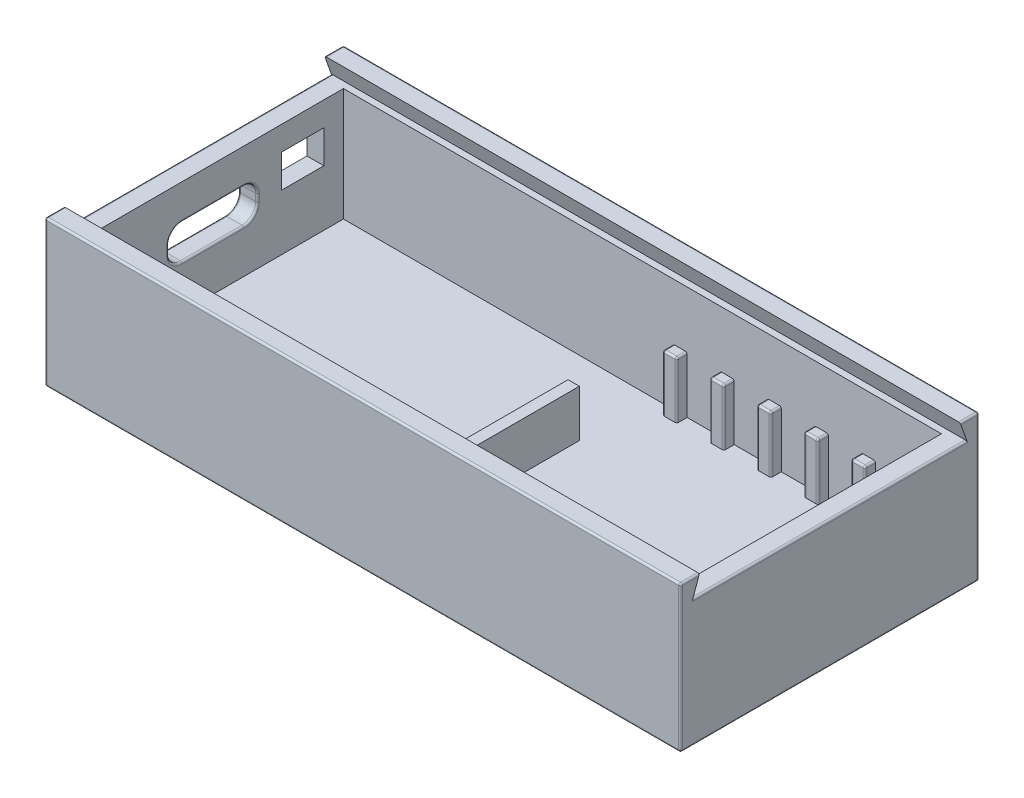
SolidWorks part; units mm, degrees
material "PLA"
ref_plane "前视基准面" through (0, 0, 0) normal (0, 0, 1) x (1, 0, 0)
ref_plane "上视基准面" through (0, 0, 0) normal (0, 1, 0) x (1, 0, 0)
ref_plane "右视基准面" through (0, 0, 0) normal (1, 0, 0) x (0, 0, -1)
sketch "草图1" plane through (0, 0, 0) normal (0, 0, 1) x (1, 0, 0)
  line L0 (0, 0) -> (67.5, 0)
  line L1 (67.5, 0) -> (67.5, 13.5)
  line L2 (67.5, 13.5) -> (65.5, 13.5)
  line L3 (65.5, 13.5) -> (65.5, 1.5)
  line L4 (65.5, 1.5) -> (2, 1.5)
  line L5 (2, 1.5) -> (2, 13.5)
  line L6 (2, 13.5) -> (0, 13.5)
  line L7 (0, 13.5) -> (0, 0)
  dimension "D1" = 63.5
  dimension "D3" = 2
  dimension "D4" = 1.5
  dimension "D6" = 12
extrude "凸台-拉伸1" add sketch "草图1" along normal blind 31.7
sketch "草图3" plane through (0, 1.5, 0) normal (0, 1, 0) x (1, 0, 0)
  line L0 (2, -31.7) -> (65.5, -31.7)
  line L1 (65.5, -31.7) -> (65.5, -29.7)
  line L2 (65.5, -31.7) -> (65.5, 0) construction
  line L3 (65.5, -29.7) -> (2, -29.7)
  line L4 (2, -31.7) -> (2, 0) construction
  line L5 (2, -29.7) -> (2, -31.7)
  dimension "D1" = 2
extrude "凸台-拉伸2" add sketch "草图3" along normal through all
sketch "草图4" plane through (0, 1.5, 0) normal (0, 1, 0) x (1, 0, 0)
  line L0 (2, 0) -> (65.5, 0)
  line L1 (65.5, -29.7) -> (65.5, 0) construction
  line L2 (65.5, -29.7) -> (65.5, 0) construction
  line L3 (65.5, 0) -> (65.5, -2)
  line L4 (65.5, -2) -> (2, -2)
  line L5 (2, -29.7) -> (2, 0) construction
  line L6 (2, -2) -> (2, 0)
  dimension "D1" = 2
extrude "凸台-拉伸3" add sketch "草图4" along normal through all
sketch "草图5" plane through (0, 1.5, 0) normal (0, 1, 0) x (1, 0, 0)
  line L0 (34.3, -6.415) -> (34.3, -25.7073) construction
  line L2 (23.9227, -15.85) -> (46.7103, -15.85) construction
  line L3 (2, -2) -> (65.5, -2) construction
  line L4 (65.5, -29.7) -> (2, -29.7) construction
  line L5 (34.9, -9.85) -> (33.7, -9.85)
  line L6 (33.7, -9.85) -> (33.7, -21.85)
  line L7 (34.9, -9.85) -> (34.9, -21.85)
  line L8 (34.9, -21.85) -> (33.7, -21.85)
  line L9 (2, -29.7) -> (2, -2) construction
  point P14 (34.3, -9.85)
  point P16 (34.9, -15.85)
  point P17 (33.7, -15.85)
  dimension "D1" = 1.2
  dimension "D2" = 32.3
  dimension "D3" = 12
extrude "凸台-拉伸4" add sketch "草图5" along normal blind 5 contours L6 L8 L7 L5
sketch "草图10" plane through (0, 0, 0) normal (-1, 0, 0) x (0, 0, 1)
  line L0 (5.075, 9.1862) -> (7.575, 9.1862) construction
  line L1 (5.075, 8.1862) -> (5.075, 10.1862) construction
  line L2 (7.575, 10.1862) -> (7.575, 8.1862) construction
  line L3 (6.325, 8.1862) -> (6.325, 10.1862) construction
  line L4 (7.575, 8.1862) -> (5.075, 8.1862) construction
  line L5 (5.075, 10.1862) -> (7.575, 10.1862) construction
  line L7 (8.575, 7.4362) -> (4.075, 7.4362)
  line L8 (8.575, 7.4362) -> (8.575, 10.9362)
  line L9 (8.575, 10.9362) -> (4.075, 10.9362)
  line L10 (4.075, 7.4362) -> (4.075, 10.9362)
  line L11 (8.575, 7.4362) -> (4.075, 10.9362) construction
  line L12 (8.575, 10.9362) -> (4.075, 7.4362) construction
  point P12 (6.325, 9.1862)
  dimension "D1" = 3.5
  dimension "D2" = 4.5
extrude "切除-拉伸3" cut sketch "草图10" against normal up to next
chamfer "倒角3" distance 0.2 angle 45 4 edges at (0, 7.4362, 6.325) (0, 9.1862, 8.575) (0, 9.1862, 4.075) (0, 10.9362, 6.325)
sketch "草图11" plane through (0, 0, 0) normal (-1, 0, 0) x (0, 0, 1)
  line L14 (11.13, 8.3362) -> (11.13, 7.5762)
  line L15 (12.58, 6.1262) -> (19.12, 6.1262)
  line L16 (20.57, 7.5762) -> (20.57, 8.3362)
  line L17 (19.12, 9.7862) -> (12.58, 9.7862)
  line L18 (11.13, 8.3362) -> (11.13, 7.5762)
  line L19 (12.58, 6.1262) -> (19.12, 6.1262)
  line L20 (20.57, 7.5762) -> (20.57, 8.3362)
  line L21 (19.12, 9.7862) -> (12.58, 9.7862)
  arc A8 (11.13, 7.5762) -> (12.58, 6.1262) centre (12.58, 7.5762) ccw
  arc A9 (19.12, 6.1262) -> (20.57, 7.5762) centre (19.12, 7.5762) ccw
  arc A10 (20.57, 8.3362) -> (19.12, 9.7862) centre (19.12, 8.3362) ccw
  arc A11 (12.58, 9.7862) -> (11.13, 8.3362) centre (12.58, 8.3362) ccw
  arc A12 (11.13, 7.5762) -> (12.58, 6.1262) centre (12.58, 7.5762) ccw
  arc A13 (19.12, 6.1262) -> (20.57, 7.5762) centre (19.12, 7.5762) ccw
  arc A14 (20.57, 8.3362) -> (19.12, 9.7862) centre (19.12, 8.3362) ccw
  arc A15 (12.58, 9.7862) -> (11.13, 8.3362) centre (12.58, 8.3362) ccw
  dimension "D1" = 0.3
extrude "切除-拉伸4" cut sketch "草图11" against normal up to next
sketch "草图14" plane through (0, 0, 2) normal (0, 0, 1) x (1, 0, 0)
  line L0 (63.4954, 1.5) -> (63.4954, 7.5)
  line L1 (2, 1.5) -> (65.5, 1.5) construction
  line L2 (63.4954, 7.5) -> (61.9954, 7.5)
  line L3 (61.9954, 7.5) -> (61.9954, 1.5)
  line L4 (61.9954, 1.5) -> (63.4954, 1.5)
  line L5 (65.5, 13.5) -> (65.5, 1.5) construction
  line L6 (61.1133, 1.5) -> (61.1133, 7.9181) construction
  line L7 (56.9954, 7.5) -> (56.9954, 1.5)
  line L8 (58.4954, 7.5) -> (56.9954, 7.5)
  line L9 (58.4954, 1.5) -> (58.4954, 7.5)
  line L10 (56.9954, 1.5) -> (58.4954, 1.5)
  line L11 (51.9954, 7.5) -> (51.9954, 1.5)
  line L12 (53.4954, 7.5) -> (51.9954, 7.5)
  line L13 (53.4954, 1.5) -> (53.4954, 7.5)
  line L14 (51.9954, 1.5) -> (53.4954, 1.5)
  line L15 (46.9954, 7.5) -> (46.9954, 1.5)
  line L16 (48.4954, 7.5) -> (46.9954, 7.5)
  line L17 (48.4954, 1.5) -> (48.4954, 7.5)
  line L18 (46.9954, 1.5) -> (48.4954, 1.5)
  line L19 (41.9954, 7.5) -> (41.9954, 1.5)
  line L20 (43.4954, 7.5) -> (41.9954, 7.5)
  line L21 (43.4954, 1.5) -> (43.4954, 7.5)
  line L22 (41.9954, 1.5) -> (43.4954, 1.5)
  line L23 (36.9954, 7.5) -> (36.9954, 1.5)
  line L24 (38.4954, 7.5) -> (36.9954, 7.5)
  line L25 (38.4954, 1.5) -> (38.4954, 7.5)
  line L26 (36.9954, 1.5) -> (38.4954, 1.5)
  line L27 (61.9954, 7.5) -> (56.9954, 7.5) construction
  dimension "D1" = 1.5
  dimension "D2" = 6
  dimension "D3" = 2.0046
  dimension "D4" = 0.8821
  dimension "D6" = 5
  dimension "D5" = 6
extrude "凸台-拉伸7" add sketch "草图14" along normal blind 1.1
fillet "圆角5" radius 0.2 18 edges at (63.4954, 4.5, 3.1) (62.7454, 7.5, 3.1) (61.9954, 4.5, 3.1) (58.4954, 4.5, 3.1) (57.7454, 7.5, 3.1) (56.9954, 4.5, 3.1) (53.4954, 4.5, 3.1) (52.7454, 7.5, 3.1) (51.9954, 4.5, 3.1) (48.4954, 4.5, 3.1) (47.7454, 7.5, 3.1) (46.9954, 4.5, 3.1) (43.4954, 4.5, 3.1) (42.7454, 7.5, 3.1) (41.9954, 4.5, 3.1) (38.4954, 4.5, 3.1) (37.7454, 7.5, 3.1) (36.9954, 4.5, 3.1)
fillet "圆角6" radius 0.2 24 edges at (63.4368, 7.4414, 3.0414) (62.0539, 7.4414, 3.0414) (57.0539, 7.4414, 3.0414) (58.4368, 7.4414, 3.0414) (53.4368, 7.4414, 3.0414) (48.4368, 7.4414, 3.0414) (43.4368, 7.4414, 3.0414) (38.4368, 7.4414, 3.0414) (52.0539, 7.4414, 3.0414) (47.0539, 7.4414, 3.0414) (42.0539, 7.4414, 3.0414) (37.0539, 7.4414, 3.0414) (63.4954, 7.5, 2.45) (61.9954, 7.5, 2.45) (56.9954, 7.5, 2.45) (58.4954, 7.5, 2.45) (53.4954, 7.5, 2.45) (48.4954, 7.5, 2.45) (43.4954, 7.5, 2.45) (38.4954, 7.5, 2.45) (51.9954, 7.5, 2.45) (46.9954, 7.5, 2.45) (41.9954, 7.5, 2.45) (36.9954, 7.5, 2.45)
sketch "草图15" plane through (0, 0, 29.7) normal (0, 0, -1) x (-1, 0, 0)
  line L0 (-65.5, 1.5) -> (-2, 1.5) construction
  line L1 (-63.5, 1.5) -> (-62, 1.5)
  line L2 (-63.5, 1.5) -> (-63.5, 7.5)
  line L3 (-63.5, 7.5) -> (-62, 7.5)
  line L4 (-62, 1.5) -> (-62, 7.5)
  line L5 (-65.5, 13.5) -> (-65.5, 1.5) construction
  line L6 (-58.5, 1.5) -> (-58.5, 7.5)
  line L7 (-58.5, 7.5) -> (-57, 7.5)
  line L8 (-57, 1.5) -> (-57, 7.5)
  line L9 (-58.5, 1.5) -> (-57, 1.5)
  line L10 (-53.5, 1.5) -> (-53.5, 7.5)
  line L11 (-53.5, 7.5) -> (-52, 7.5)
  line L12 (-52, 1.5) -> (-52, 7.5)
  line L13 (-53.5, 1.5) -> (-52, 1.5)
  line L14 (-48.5, 1.5) -> (-48.5, 7.5)
  line L15 (-48.5, 7.5) -> (-47, 7.5)
  line L16 (-47, 1.5) -> (-47, 7.5)
  line L17 (-48.5, 1.5) -> (-47, 1.5)
  line L18 (-43.5, 1.5) -> (-43.5, 7.5)
  line L19 (-43.5, 7.5) -> (-42, 7.5)
  line L20 (-42, 1.5) -> (-42, 7.5)
  line L21 (-43.5, 1.5) -> (-42, 1.5)
  line L22 (-38.5, 1.5) -> (-38.5, 7.5)
  line L23 (-38.5, 7.5) -> (-37, 7.5)
  line L24 (-37, 1.5) -> (-37, 7.5)
  line L25 (-38.5, 1.5) -> (-37, 1.5)
  line L26 (-63.5, 1.5) -> (-58.5, 1.5) construction
  dimension "D1" = 2
  dimension "D2" = 1.5
  dimension "D3" = 6
  dimension "D5" = 5
  dimension "D4" = 6
extrude "凸台-拉伸8" add sketch "草图15" along normal blind 1.1
fillet "圆角7" radius 0.2 30 edges at (37, 7.5, 29.15) (37.75, 7.5, 28.6) (37, 4.5, 28.6) (38.5, 4.5, 28.6) (38.5, 7.5, 29.15) (42, 4.5, 28.6) (43.5, 4.5, 28.6) (42, 7.5, 29.15) (42.75, 7.5, 28.6) (43.5, 7.5, 29.15) (47, 7.5, 29.15) (47, 4.5, 28.6) (47.75, 7.5, 28.6) (48.5, 4.5, 28.6) (48.5, 7.5, 29.15) (52, 7.5, 29.15) (52.75, 7.5, 28.6) (52, 4.5, 28.6) (53.5, 4.5, 28.6) (53.5, 7.5, 29.15) (58.5, 7.5, 29.15) (57, 7.5, 29.15) (57.75, 7.5, 28.6) (57, 4.5, 28.6) (58.5, 4.5, 28.6) (63.5, 4.5, 28.6) (62, 4.5, 28.6) (62, 7.5, 29.15) (62.75, 7.5, 28.6) (63.5, 7.5, 29.15)
sketch "草图16" plane through (0, 0, 0) normal (-1, 0, 0) x (0, 0, 1)
  line L0 (0, 13.5) -> (0, 15.5)
  line L1 (0, 15.5) -> (2, 15.5)
  line L2 (2, 15.5) -> (1.3, 13.5)
  line L3 (31.7, 13.5) -> (0, 13.5) construction
  line L4 (1.3, 13.5) -> (0, 13.5)
  line L5 (15.85, 0) -> (15.85, 20.1555) construction
  line L6 (31.7, 0) -> (0, 0) construction
  line L7 (30.4, 13.5) -> (31.7, 13.5)
  line L8 (29.7, 15.5) -> (30.4, 13.5)
  line L9 (31.7, 15.5) -> (29.7, 15.5)
  line L10 (31.7, 13.5) -> (31.7, 15.5)
  dimension "D1" = 2
  dimension "D2" = 2
  dimension "D3" = 1.3
extrude "凸台-拉伸9" add sketch "草图16" against normal through all
fillet "圆角8" radius 0.2 8 edges at (0, 6.5509, 20.1453) (0, 6.1262, 15.85) (0, 6.5509, 11.5547) (0, 7.9562, 11.13) (0, 9.3615, 11.5547) (0, 9.7862, 15.85) (0, 9.3615, 20.1453) (0, 7.9562, 20.57)
fillet "圆角9" radius 0.2 4 edges at (67.5, 13.5, 15.85) (0, 13.5, 15.85) (33.75, 15.5, 0) (33.75, 15.5, 31.7)
fillet "圆角10" radius 0.2 16 edges at (67.5, 15.5, 1.1) (67.5, 15.4414, 0.0586) (67.5, 15.5, 30.6) (67.5, 15.4414, 31.6414) (0, 15.5, 30.6) (0, 15.4414, 31.6414) (0, 15.5, 1.1) (0, 15.4414, 0.0586) (33.75, 0, 0) (67.5, 0, 15.85) (67.5, 7.65, 0) (67.5, 7.65, 31.7) (33.75, 0, 31.7) (0, 7.65, 31.7) (0, 0, 15.85) (0, 7.65, 0)
fillet "圆角11" radius 0.2 8 edges at (2, 6.5509, 20.1453) (2, 7.9562, 20.57) (2, 9.3615, 20.1453) (2, 9.7862, 15.85) (2, 9.3615, 11.5547) (2, 7.9562, 11.13) (2, 6.5509, 11.5547) (2, 6.1262, 15.85)
